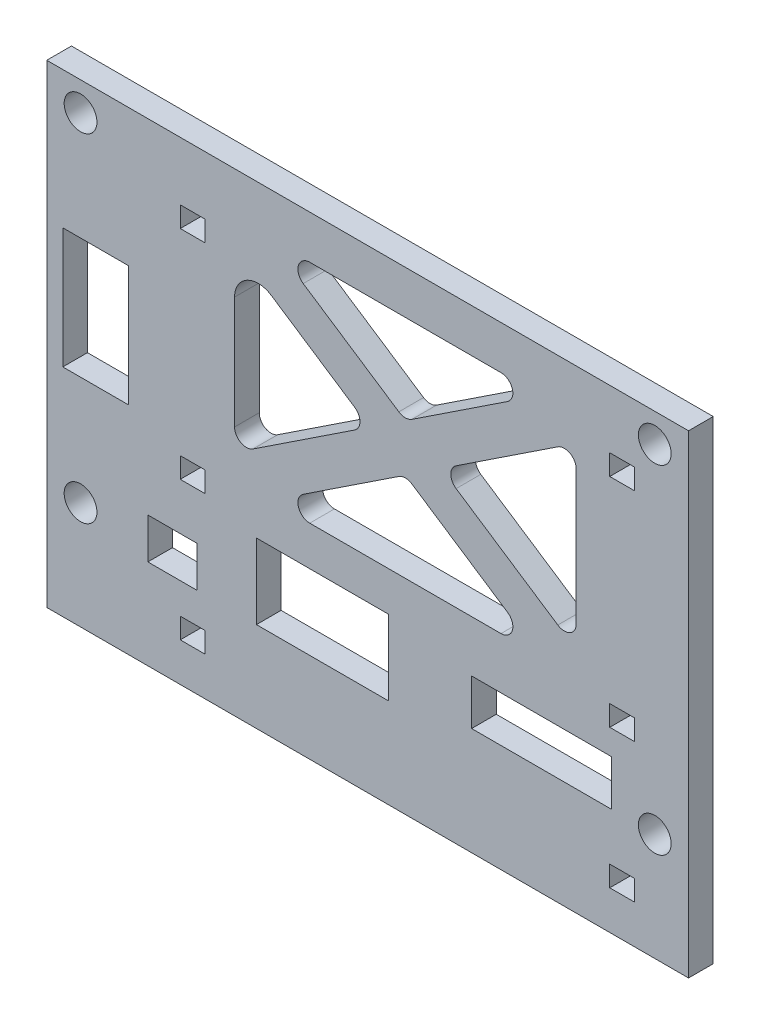
SolidWorks part; units mm, degrees
material "Beech"
ref_plane "Front Plane" through (0, 0, 0) normal (0, 0, 1) x (1, 0, 0)
ref_plane "Top Plane" through (0, 0, 0) normal (0, 1, 0) x (1, 0, 0)
ref_plane "Right Plane" through (0, 0, 0) normal (1, 0, 0) x (0, 0, -1)
sketch "Sketch1" plane through (0, 0, 0) normal (0, 0, 1) x (1, 0, 0)
  line L0 (-20.6375, 0) -> (20.6375, 0)
  line L2 (-20.6375, 0) -> (20.6375, 0)
  line L3 (-20.6375, 0) -> (-20.6375, -5.08)
  line L4 (-20.6375, -5.08) -> (20.6375, -5.08)
  line L5 (20.6375, 0) -> (20.6375, -5.08)
  line L44 (0, 14.605) -> (0, 24.13) construction
  line L46 (-20.6375, 0) -> (-20.6375, 25.4)
  line L47 (-20.6375, 25.4) -> (20.6375, 25.4)
  line L48 (20.6375, 0) -> (20.6375, 25.4)
  line L49 (-20.6375, 12.7) -> (20.6375, 12.7) construction
  circle A2 centre (-18.4658, 23.5585) radius 1.0541
  circle A3 centre (-18.4658, 1.8415) radius 1.0541
  circle A4 centre (18.4658, 1.8415) radius 1.0541
  circle A5 centre (18.4658, 23.5585) radius 1.0541
  point P0 (0, 0)
  point P56 (0, 12.7)
  point P60 (0, 25.4)
  dimension "D14" = 12.7
  dimension "D4" = 2.1082
  dimension "D2" = 5.08
  dimension "D3" = 25.4
  dimension "D12" = 41.275
  dimension "D5" = 2.1717
  dimension "D6" = 1.8415
extrude "Boss-Extrude1" add sketch "Sketch1" along normal blind 1.5875 contours L48 L47 L46 | L5 L0 L3 L4 region at (0, 12.7, 0) region at (0, -2.54, 0)
sketch "Sketch2" plane through (0, 0, 1.5875) normal (0, 0, 1) x (1, 0, 0)
  line L4 (6.6858, 1.8395) -> (15.6858, 1.8395)
  line L5 (6.6858, 4.7695) -> (6.6858, 1.8395)
  line L6 (15.6858, 4.7695) -> (6.6858, 4.7695)
  line L7 (15.6858, 1.8395) -> (15.6858, 4.7695)
  line L8 (6.6858, 1.8395) -> (15.6858, 1.8395)
  line L9 (6.6858, 4.7695) -> (6.6858, 1.8395)
  line L10 (15.6858, 4.7695) -> (6.6858, 4.7695)
  line L11 (15.6858, 1.8395) -> (15.6858, 4.7695)
  line L12 (1.3552, 5.5335) -> (-7.1538, 5.5335)
  line L13 (1.3552, 0.7075) -> (1.3552, 5.5335)
  line L14 (-7.1538, 0.7075) -> (1.3552, 0.7075)
  line L15 (-7.1538, 5.5335) -> (-7.1538, 0.7075)
  line L16 (1.3552, 5.5335) -> (-7.1538, 5.5335)
  line L17 (1.3552, 0.7075) -> (1.3552, 5.5335)
  line L18 (-7.1538, 0.7075) -> (1.3552, 0.7075)
  line L19 (-7.1538, 5.5335) -> (-7.1538, 0.7075)
  line L20 (-10.9638, 3.3237) -> (-14.1388, 3.3237)
  line L21 (-10.9638, 0.7075) -> (-10.9638, 3.3237)
  line L22 (-14.1388, 0.7075) -> (-10.9638, 0.7075)
  line L23 (-14.1388, 3.3237) -> (-14.1388, 0.7075)
  line L24 (-10.9638, 3.3237) -> (-14.1388, 3.3237)
  line L25 (-10.9638, 0.7075) -> (-10.9638, 3.3237)
  line L26 (-14.1388, 0.7075) -> (-10.9638, 0.7075)
  line L27 (-14.1388, 3.3237) -> (-14.1388, 0.7075)
  line L28 (-19.6078, 8.834) -> (-15.3878, 8.834)
  line L29 (-19.6078, 16.584) -> (-19.6078, 8.834)
  line L30 (-15.3878, 16.584) -> (-19.6078, 16.584)
  line L31 (-15.3878, 8.834) -> (-15.3878, 16.584)
  line L32 (-19.6078, 8.834) -> (-15.3878, 8.834)
  line L33 (-19.6078, 16.584) -> (-19.6078, 8.834)
  line L34 (-15.3878, 16.584) -> (-19.6078, 16.584)
  line L35 (-15.3878, 8.834) -> (-15.3878, 16.584)
  line L48 (15.5702, 20.32) -> (15.5702, 21.6408) construction
  line L49 (15.5702, 21.6408) -> (17.1577, 21.6408) construction
  line L50 (17.1577, 21.6408) -> (17.1577, 20.32) construction
  line L51 (17.1577, 20.32) -> (15.5702, 20.32) construction
  line L52 (15.5702, 6.35) -> (15.5702, 7.6708) construction
  line L53 (15.5702, 7.6708) -> (17.1577, 7.6708) construction
  line L54 (17.1577, 7.6708) -> (17.1577, 6.35) construction
  line L55 (17.1577, 6.35) -> (15.5702, 6.35) construction
  line L56 (15.5702, -2.5908) -> (15.5702, -1.27) construction
  line L57 (15.5702, -1.27) -> (17.1577, -1.27) construction
  line L58 (17.1577, -1.27) -> (17.1577, -2.5908) construction
  line L59 (17.1577, -2.5908) -> (15.5702, -2.5908) construction
  line L60 (-12.0523, -2.5908) -> (-12.0523, -1.27) construction
  line L61 (-12.0523, -1.27) -> (-10.4648, -1.27) construction
  line L62 (-10.4648, -1.27) -> (-10.4648, -2.5908) construction
  line L63 (-10.4648, -2.5908) -> (-12.0523, -2.5908) construction
  line L64 (-8.5598, 21.0833) -> (11.1091, 8.0735)
  line L65 (-8.5598, 22.606) -> (13.4112, 22.606)
  line L66 (-8.5598, 22.606) -> (-8.5598, 8.0735)
  line L67 (-8.5598, 8.0735) -> (13.4112, 8.0735)
  line L68 (13.4112, 22.606) -> (13.4112, 8.0735)
  line L69 (-8.5598, 22.606) -> (13.4112, 8.0735) construction
  line L70 (-8.5598, 8.0735) -> (13.4112, 22.606) construction
  line L71 (-6.2577, 22.606) -> (13.4112, 9.5962)
  line L72 (-6.2577, 8.0735) -> (13.4112, 21.0833)
  line L73 (-8.5598, 9.5962) -> (11.1091, 22.606)
  line L74 (-7.8592, 7.0142) -> (14.1118, 21.5467) construction
  line L75 (-9.2604, 9.1328) -> (12.7106, 23.6653) construction
  line L76 (-9.2604, 21.5467) -> (12.7106, 7.0142) construction
  line L77 (-7.8592, 23.6653) -> (14.1118, 9.1328) construction
  line L78 (-20.6375, 25.4) -> (20.6375, 25.4) construction
  line L87 (-12.0523, 6.35) -> (-12.0523, 7.6708) construction
  line L88 (-12.0523, 7.6708) -> (-10.4648, 7.6708) construction
  line L89 (-10.4648, 7.6708) -> (-10.4648, 6.35) construction
  line L90 (-10.4648, 6.35) -> (-12.0523, 6.35) construction
  line L91 (-12.0523, 20.32) -> (-12.0523, 21.6408) construction
  line L92 (-12.0523, 21.6408) -> (-10.4648, 21.6408) construction
  line L93 (-10.4648, 21.6408) -> (-10.4648, 20.32) construction
  line L94 (-10.4648, 20.32) -> (-12.0523, 20.32) construction
  line L95 (15.5702, 20.32) -> (15.5702, 21.6408)
  line L96 (15.5702, 21.6408) -> (17.1577, 21.6408)
  line L97 (17.1577, 21.6408) -> (17.1577, 20.32)
  line L98 (17.1577, 20.32) -> (15.5702, 20.32)
  line L99 (15.5702, 6.35) -> (15.5702, 7.6708)
  line L100 (15.5702, 7.6708) -> (17.1577, 7.6708)
  line L101 (17.1577, 7.6708) -> (17.1577, 6.35)
  line L102 (17.1577, 6.35) -> (15.5702, 6.35)
  line L103 (15.5702, -2.5908) -> (15.5702, -1.27)
  line L104 (15.5702, -1.27) -> (17.1577, -1.27)
  line L105 (17.1577, -1.27) -> (17.1577, -2.5908)
  line L106 (17.1577, -2.5908) -> (15.5702, -2.5908)
  line L107 (-12.0523, -2.5908) -> (-12.0523, -1.27)
  line L108 (-12.0523, -1.27) -> (-10.4648, -1.27)
  line L109 (-10.4648, -1.27) -> (-10.4648, -2.5908)
  line L110 (-10.4648, -2.5908) -> (-12.0523, -2.5908)
  line L111 (-12.0523, 6.35) -> (-12.0523, 7.6708)
  line L112 (-12.0523, 7.6708) -> (-10.4648, 7.6708)
  line L113 (-10.4648, 7.6708) -> (-10.4648, 6.35)
  line L114 (-10.4648, 6.35) -> (-12.0523, 6.35)
  line L115 (-12.0523, 20.32) -> (-12.0523, 21.6408)
  line L116 (-12.0523, 21.6408) -> (-10.4648, 21.6408)
  line L117 (-10.4648, 21.6408) -> (-10.4648, 20.32)
  line L118 (-10.4648, 20.32) -> (-12.0523, 20.32)
  point P30 (2.4257, 15.3398)
  dimension "D9" = 2.794
  dimension "D10" = 2.54
  dimension "D11" = 2.159
  dimension "D12" = 1.905
  dimension "D1" = 0
  dimension "D2" = 0
  dimension "D3" = 0
  dimension "D4" = 0
  dimension "D5" = 1.27
  dimension "D6" = 1.27
  dimension "D7" = 1.27
  dimension "D8" = 1.27
extrude "Cut-Extrude1" cut sketch "Sketch2" against normal up to surface (1.5875 mm away) contours L98 L97 L96 L95 | L8 L11 L10 L9 | L72 L67 L64 | L72 L71 L68 | L71 L73 L65 | L66 L73 L64 | L118 L117 L116 L115 | L16 L19 L18 L17 | L32 L35 L34 L33 | L114 L113 L112 L111 | L24 L27 L26 L25 | L110 L109 L108 L107 | L99 L100 L101 L102 | L103 L104 L105 L106 region at (11.1858, 3.3045, 1.5875) region at (-2.8993, 3.1205, 1.5875) region at (-12.5513, 2.0156, 1.5875) region at (-17.4978, 12.709, 1.5875) region at (-5.6653, 15.3398, 1.5875) region at (2.4257, 9.988, 1.5875) region at (2.4257, 20.6915, 1.5875) region at (10.5167, 15.3398, 1.5875) region at (16.364, 20.9804, 1.5875) region at (-11.2585, -1.9304, 1.5875) region at (-11.2585, 7.0104, 1.5875) region at (-11.2585, 20.9804, 1.5875) up to face at (-17.4117, 1.8415, 0)
fillet "Fillet8" radius 0.762 11 edges at (-6.2577, 8.0735, 0.7937) (-8.5598, 9.5962, 0.7937) (11.1091, 8.0735, 0.7937) (13.4112, 9.5962, 0.7937) (13.4112, 21.0833, 0.7937) (11.1091, 22.606, 0.7937) (-6.2577, 22.606, 0.7937) (2.4257, 13.8171, 0.7937) (4.7278, 15.3398, 0.7937) (2.4257, 16.8624, 0.7937) (0.1236, 15.3398, 0.7937)
fillet "Fillet9" radius 1.524 1 edges at (-8.5598, 21.0833, 0.7937)
